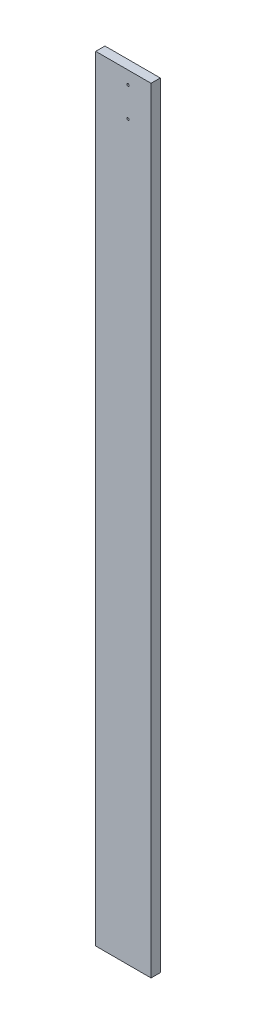
SolidWorks part; units mm, degrees
ref_plane "Front Plane" through (0, 0, 0) normal (0, 0, 1) x (1, 0, 0)
ref_plane "Top Plane" through (0, 0, 0) normal (0, 1, 0) x (1, 0, 0)
ref_plane "Right Plane" through (0, 0, 0) normal (1, 0, 0) x (0, 0, -1)
sketch "Sketch1" plane through (0, 0, 0) normal (0, 0, 1) x (1, 0, 0)
  line L1 (-25.4, -292.1) -> (-25.4, 241.3) construction
  line L2 (-25.4, 241.3) -> (12.7, 241.3)
  line L3 (-25.4, 241.3) -> (-25.4, -292.1)
  line L4 (-25.4, -292.1) -> (12.7, -292.1)
  line L5 (12.7, 241.3) -> (12.7, -292.1)
  point P6 (-25.4, -25.4)
  dimension "D1" = 533.4
  dimension "D2" = 38.1
  dimension "D3" = 12.7
  dimension "D4" = 241.3
extrude "Boss-Extrude1" add sketch "Sketch1" along normal mid plane 6.35
sketch "Sketch2" plane through (0, 0, 3.175) normal (0, 0, 1) x (1, 0, 0)
  line L0 (12.7, 241.3) -> (-25.4, 241.3) construction
  line L1 (-3.16, 241.3) -> (-3.16, 205.7623) construction
  line L2 (-25.4, 241.3) -> (-25.4, -292.1) construction
  circle A0 centre (-3.16, 232.41) radius 0.7937
  circle A1 centre (-3.16, 212.09) radius 0.7938
  dimension "D3" = 1.5875
  dimension "D1" = 8.89
  dimension "D2" = 20.32
  dimension "D4" = 22.24
extrude "Cut-Extrude1" cut sketch "Sketch2" against normal through all
move or copy body "Body-Move/Copy1" [suppressed] bodies to move or copy 102 parameters "D1"=0, "D2"=0, "D3"=0
